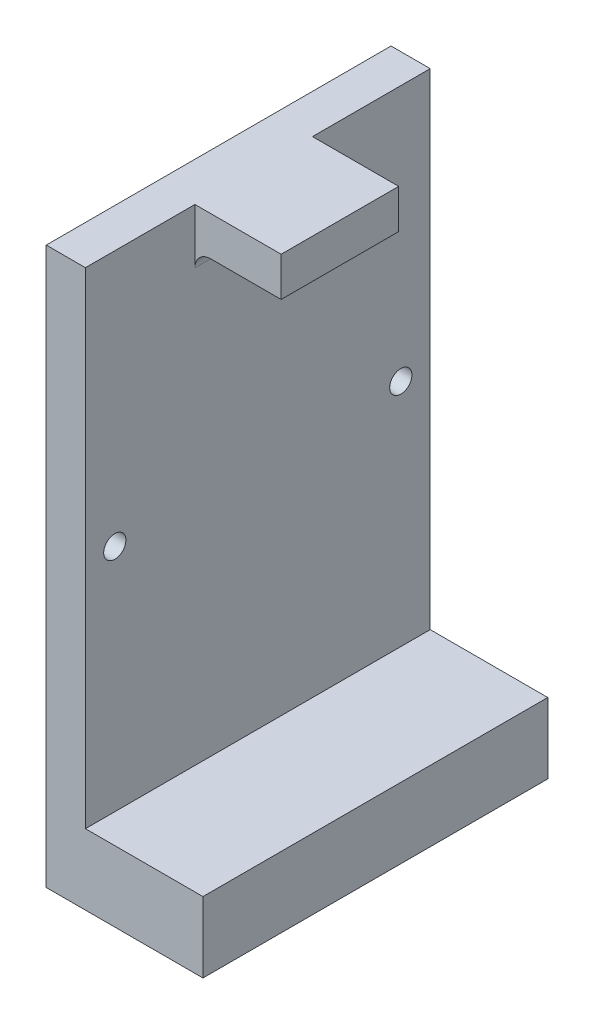
SolidWorks part; units mm, degrees
ref_plane "Front Plane" through (0, 0, 0) normal (0, 0, 1) x (1, 0, 0)
ref_plane "Top Plane" through (0, 0, 0) normal (0, 1, 0) x (1, 0, 0)
ref_plane "Right Plane" through (0, 0, 0) normal (1, 0, 0) x (0, 0, -1)
sketch "Sketch1" plane through (0, 0, 0) normal (0, 1, 0) x (1, 0, 0)
  line L1 (0, 0) -> (-25.4, 0)
  line L2 (0, 0) -> (0, 55.88)
  line L3 (0, 55.88) -> (-25.4, 55.88)
  line L4 (-25.4, 0) -> (-25.4, 55.88)
  dimension "D1" = 55.88
  dimension "D2" = 25.4
extrude "Boss-Extrude1" add sketch "Sketch1" along normal blind 11.43
sketch "Sketch3" plane through (0, 11.43, 0) normal (0, 1, 0) x (1, 0, 0)
  line L0 (-25.4, 0) -> (0, 0) construction
  line L1 (-25.4, 55.88) -> (-19.05, 55.88)
  line L2 (-25.4, 55.88) -> (-25.4, 0)
  line L3 (-25.4, 0) -> (-19.05, 0)
  line L4 (-19.05, 55.88) -> (-19.05, 0)
  dimension "D1" = 6.35
extrude "Boss-Extrude2" add sketch "Sketch3" along normal blind 78.74
sketch "Sketch4" plane through (-19.05, 0, 0) normal (1, 0, 0) x (0, 0, -1)
  line L0 (0, 90.17) -> (55.88, 90.17) construction
  line L1 (17.7495, 90.17) -> (36.7995, 90.17)
  line L2 (17.7495, 90.17) -> (17.7495, 83.82)
  line L3 (17.7495, 83.82) -> (36.7995, 83.82)
  line L4 (36.7995, 90.17) -> (36.7995, 83.82)
  dimension "D1" = 19.05
  dimension "D2" = 6.35
extrude "Boss-Extrude3" add sketch "Sketch4" along normal blind 13.97
hole_wizard "M3 Clearance Hole1" positions "Sketch5" profile "Sketch6" hole size "M3" standard "ANSI Metric" end condition through all
sketch "Sketch5" plane through (-19.05, 0, 0) normal (1, 0, 0) x (0, 0, -1)
  line L0 (0, 90.17) -> (0, 11.43) construction
  point P0 (4.7625, 48.6673)
  point P2 (51.1175, 48.6673)
  dimension "D1" = 46.355
  dimension "D2" = 4.7625
sketch "Sketch6" plane through (-19.05, 48.6673, -4.7625) normal (0, 1, 0) x (0, 0, -1)
  line L0 (0, 0) -> (0, 6.35)
  line L1 (0, 6.35) -> (1.8, 6.35)
  line L2 (1.8, 6.35) -> (1.8, 0)
  line L5 (1.8, 0) -> (0, 0)
  line L11 (0, -6.35) -> (0, 107.95) construction
  dimension "Thru Hole Dia." = 3.6
  dimension "Thru Hole Depth" = 6.35
fillet "Fillet1" radius 2.54 1 edges at (-19.05, 83.82, -27.2745)
